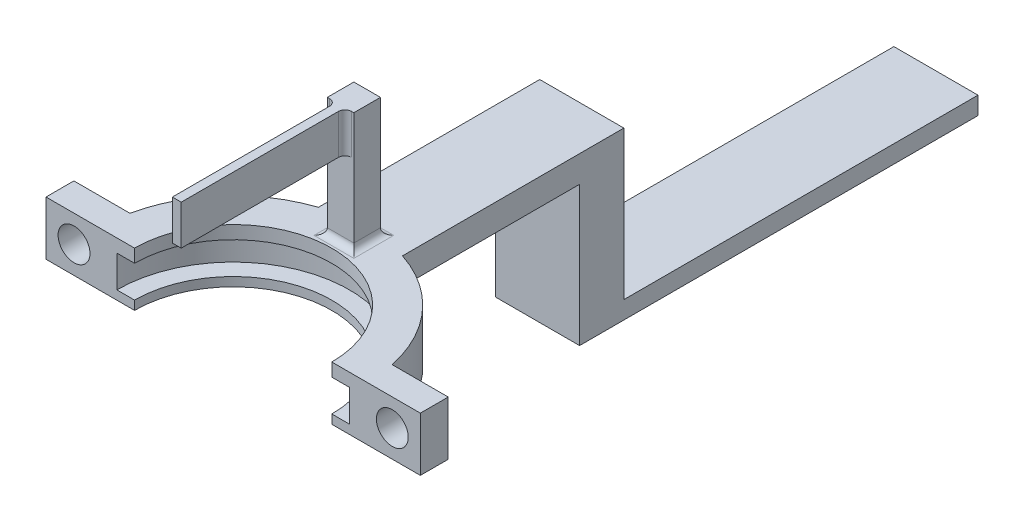
SolidWorks part; units mm, degrees
ref_plane "Front Plane" through (0, 0, 0) normal (0, 0, 1) x (1, 0, 0)
ref_plane "Top Plane" through (0, 0, 0) normal (0, 1, 0) x (1, 0, 0)
ref_plane "Right Plane" through (0, 0, 0) normal (1, 0, 0) x (0, 0, -1)
sketch "Sketch3" plane through (0, 0, 0) normal (0, 0, 1) x (1, 0, 0)
  line L2 (-62.6943, 11.7337) -> (-64.8845, 11.7337)
  line L3 (-62.8845, 10.2507) -> (-60.8845, 10.2507)
  line L5 (-60.8845, 6.6507) -> (-62.8845, 6.6507)
  line L6 (-62.8845, 6.6507) -> (-62.8845, 10.2507)
  line L10 (-64.8845, 11.7337) -> (-64.8845, 5.6398)
  line L11 (-64.8845, 5.6398) -> (-60.8845, 5.6398)
  line L12 (-60.8845, 5.6398) -> (-60.8845, 6.6507)
  line L13 (-60.8845, 10.2507) -> (-60.8845, 11.7337)
  line L14 (-60.8845, 11.7337) -> (-62.6943, 11.7337)
  dimension "D2" = 2
  dimension "D3" = 4
  dimension "D1" = 2
sketch "Sketch4" plane through (0, 0, 0) normal (0, 0, 1) x (1, 0, 0)
  line L0 (-49.7443, 0) -> (-49.7443, 12.8648) construction
  line L1 (27.6543, 0) -> (-27.6543, 0) construction
revolve "Revolve1" add sketch "Sketch3" angle 360 about L0
sketch "Sketch7" plane through (0, 11.7337, 0) normal (0, 1, 0) x (1, 0, 0)
  line L2 (-50.2443, 15.132) -> (-50.2443, 13.1308)
  line L3 (-49.2443, 15.132) -> (-49.2443, 13.1308)
  circle A0 centre (-49.7443, 0) radius 15.1403 construction
  arc A1 (-49.2443, 15.132) -> (-50.2443, 15.132) centre (-49.7443, 0) ccw
  circle A2 centre (-49.7443, 0) radius 13.1403 construction
  arc A3 (-49.2443, 13.1308) -> (-50.2443, 13.1308) centre (-49.7443, 0) ccw
  point P9 (-49.7443, 14.131)
  dimension "D1" = 1
extrude "Boss-Extrude1" add sketch "Sketch7" along normal blind 12
sketch "Sketch8" plane through (0, 23.7337, 0) normal (0, 1, 0) x (1, 0, 0)
  line L0 (-50.2443, 15.132) -> (-50.2443, 13.1308) construction
  line L3 (-50.2443, 15.132) -> (-50.2443, 13.1308)
  line L4 (-49.2443, 13.1308) -> (-49.2443, 15.132) construction
  line L5 (-49.2443, 13.1308) -> (-49.2443, 15.132)
  line L6 (-50.2443, 13.1308) -> (-50.2443, -6.3692)
  line L7 (-50.2443, -6.3692) -> (-49.2443, -6.3692)
  line L8 (-49.2443, -6.3692) -> (-49.2443, 13.1308)
  arc A0 (-49.2443, 15.132) -> (-50.2443, 15.132) centre (-49.7443, 0) ccw construction
  arc A1 (-49.2443, 15.132) -> (-50.2443, 15.132) centre (-49.7443, 0) ccw
  dimension "D1" = 19.5
extrude "Boss-Extrude2" add sketch "Sketch8" against normal blind 3
sketch "Sketch9" plane through (0, 11.7337, 0) normal (0, 1, 0) x (1, 0, 0)
  line L2 (-54.4943, 14.3759) -> (-54.4943, 39.3759)
  line L3 (-54.4943, 39.3759) -> (-44.9943, 39.3759)
  line L4 (-44.9943, 39.3759) -> (-44.9943, 14.3759)
  arc A0 (-50.2443, 15.132) -> (-49.2443, 15.132) centre (-49.7443, 0) ccw construction
  arc A1 (-50.2443, 15.132) -> (-54.4943, 14.3759) centre (-49.7443, 0) ccw
  arc A2 (-49.2443, 15.132) -> (-50.2443, 15.132) centre (-49.7443, 0) ccw construction
  arc A3 (-49.2443, 15.132) -> (-50.2443, 15.132) centre (-49.7443, 0) ccw
  arc A4 (-44.9943, 14.3759) -> (-49.2443, 15.132) centre (-49.7443, 0) ccw
  point P9 (-49.7443, 0)
  dimension "D1" = 25
extrude "Boss-Extrude3" add sketch "Sketch9" against normal blind 3
sketch "Sketch10" plane through (0, 8.7337, 0) normal (0, -1, 0) x (1, 0, 0)
  line L0 (-44.9943, -14.3759) -> (-44.9943, -39.3759) construction
  line L1 (-54.4943, -39.3759) -> (-44.9943, -39.3759)
  line L2 (-54.4943, -39.3759) -> (-54.4943, -34.3759)
  line L3 (-54.4943, -34.3759) -> (-44.9943, -34.3759)
  line L4 (-44.9943, -39.3759) -> (-44.9943, -34.3759)
  dimension "D1" = 5
extrude "Boss-Extrude4" add sketch "Sketch10" along normal blind 15.78
sketch "Sketch11" plane through (0, 0, -39.3759) normal (0, 0, -1) x (-1, 0, 0)
  line L0 (54.4943, -7.0463) -> (54.4943, 11.7337) construction
  line L1 (44.9943, -7.0463) -> (54.4943, -7.0463)
  line L2 (44.9943, -7.0463) -> (44.9943, -5.0463)
  line L3 (44.9943, -5.0463) -> (54.4943, -5.0463)
  line L4 (54.4943, -7.0463) -> (54.4943, -5.0463)
  dimension "D1" = 2
extrude "Boss-Extrude5" add sketch "Sketch11" along normal blind 40
sketch "Sketch13" plane through (0, 11.7337, 0) normal (0, 1, 0) x (1, 0, 0)
  line L2 (-49.7443, 3.15) -> (-49.7443, -3.15) construction
  line L3 (-28.604, 3.15) -> (-34.9353, 3.15)
  line L4 (-70.8845, 3.15) -> (-70.8845, -3.15)
  line L5 (-70.8845, -3.15) -> (-64.5532, -3.15)
  line L6 (-28.604, -3.15) -> (-28.604, 3.15)
  line L7 (-64.5532, 3.15) -> (-70.8845, 3.15)
  line L8 (-34.9353, -3.15) -> (-28.604, -3.15)
  arc A0 (-54.4943, 14.3759) -> (-44.9943, 14.3759) centre (-49.7443, 0) ccw construction
  arc A1 (-64.5532, 3.15) -> (-64.5532, -3.15) centre (-49.7443, 0) ccw
  arc A2 (-34.9353, -3.15) -> (-34.9353, 3.15) centre (-49.7443, 0) ccw
  point P10 (-49.7443, 0)
  point P13 (-49.7443, 3.15)
  dimension "D1" = 6.3
extrude "Boss-Extrude6" add sketch "Sketch13" against normal up to surface (6.0939 mm away) up to face at (-49.7443, 5.6398, -11.1403)
sketch "Sketch14" plane through (0, 0, 3.15) normal (0, 0, 1) x (1, 0, 0)
  line L0 (-70.8845, 11.7337) -> (-64.5532, 5.6398) construction
  line L1 (-28.604, 11.7337) -> (-34.9353, 5.6398) construction
  circle A0 centre (-31.7697, 8.6868) radius 1.8
  circle A1 centre (-67.7189, 8.6868) radius 1.8
  dimension "D1" = 3.6
  dimension "D2" = 3.6
extrude "Cut-Extrude1" cut sketch "Sketch14" against normal up to surface (6.3 mm away) contours A1 | A0 up to face at (-67.7189, 8.6868, -3.15)
sketch "Sketch15" plane through (0, 11.7337, 0) normal (0, 1, 0) x (1, 0, 0)
  line L0 (-70.8845, 0) -> (-23.4421, 0) construction
  line L1 (-70.8845, 3.15) -> (-70.8845, -3.15) construction
  line L2 (-13.0536, 0) -> (13.0536, 0) construction
  line L4 (-23.4421, 0) -> (-74.5953, 0)
  line L5 (-23.4421, 0) -> (-23.4421, -21.2106)
  line L6 (-23.4421, -21.2106) -> (-74.5953, -21.2106)
  line L7 (-74.5953, 0) -> (-74.5953, -21.2106)
extrude "Cut-Extrude3" cut sketch "Sketch15" against normal through all
sketch "Sketch16" plane through (0, 0, 0) normal (0, 1, 0) x (1, 0, 0)
  line L1 (-54.8883, 5.4174) -> (-45.2843, 5.4174)
  line L2 (-54.8883, 5.4174) -> (-54.8883, -6.4675)
  line L3 (-54.8883, -6.4675) -> (-45.2843, -6.4675)
  line L4 (-45.2843, 5.4174) -> (-45.2843, -6.4675)
sketch "Sketch18" plane through (0, 11.7337, 0) normal (0, 1, 0) x (1, 0, 0)
  line L0 (-50.2443, 15.132) -> (-49.2443, 15.132) construction
  line L1 (-48.2443, 15.132) -> (-51.2443, 15.132)
  line L2 (-51.2443, 15.132) -> (-51.2443, 12.132)
  line L3 (-51.2443, 12.132) -> (-48.2443, 12.132)
  line L4 (-48.2443, 12.132) -> (-48.2443, 15.132)
  point P7 (-49.7443, 15.132)
  dimension "D1" = 3
  dimension "D2" = 3
extrude "Boss-Extrude7" add sketch "Sketch18" along normal up to surface (12 mm away) up to face at (-49.7443, 23.7337, -4.3834)
fillet "Fillet1" radius 0.75 6 edges at (-49.7443, 11.7337, -12.132) (-48.7443, 11.7337, -15.132) (-49.7443, 11.7337, -15.1403) (-50.7443, 11.7337, -15.132) (-51.2443, 11.7337, -13.632) (-48.2443, 11.7337, -13.632)
sketch "Sketch19" plane through (0, 23.7337, 0) normal (0, 1, 0) x (1, 0, 0)
  line L18 (-50.2443, 15.132) -> (-51.2443, 15.132)
  line L19 (-51.2443, 15.132) -> (-51.2443, 12.132)
  line L20 (-51.2443, 12.132) -> (-50.2443, 12.132)
  line L21 (-50.2443, 12.132) -> (-50.2443, -6.3692)
  line L22 (-50.2443, -6.3692) -> (-49.2443, -6.3692)
  line L23 (-49.2443, -6.3692) -> (-49.2443, 12.132)
  line L24 (-49.2443, 12.132) -> (-48.2443, 12.132)
  line L25 (-48.2443, 12.132) -> (-48.2443, 15.132)
  line L26 (-48.2443, 15.132) -> (-49.2443, 15.132)
  line L27 (-50.2443, 15.132) -> (-51.2443, 15.132)
  line L28 (-51.2443, 15.132) -> (-51.2443, 12.132)
  line L29 (-51.2443, 12.132) -> (-50.2443, 12.132)
  line L30 (-50.2443, 12.132) -> (-50.2443, -6.3692)
  line L31 (-50.2443, -6.3692) -> (-49.2443, -6.3692)
  line L32 (-49.2443, -6.3692) -> (-49.2443, 12.132)
  line L33 (-49.2443, 12.132) -> (-48.2443, 12.132)
  line L34 (-48.2443, 12.132) -> (-48.2443, 15.132)
  line L35 (-48.2443, 15.132) -> (-49.2443, 15.132)
  arc A2 (-49.2443, 15.132) -> (-50.2443, 15.132) centre (-49.7443, 0) ccw
  arc A3 (-49.2443, 15.132) -> (-50.2443, 15.132) centre (-49.7443, 0) ccw
  dimension "D1" = 0
extrude "Boss-Extrude8" add sketch "Sketch19" along normal blind 1.5
fillet "Fillet2" radius 0.75 2 edges at (-49.2443, 22.9837, -12.132) (-50.2443, 22.9837, -12.132)
